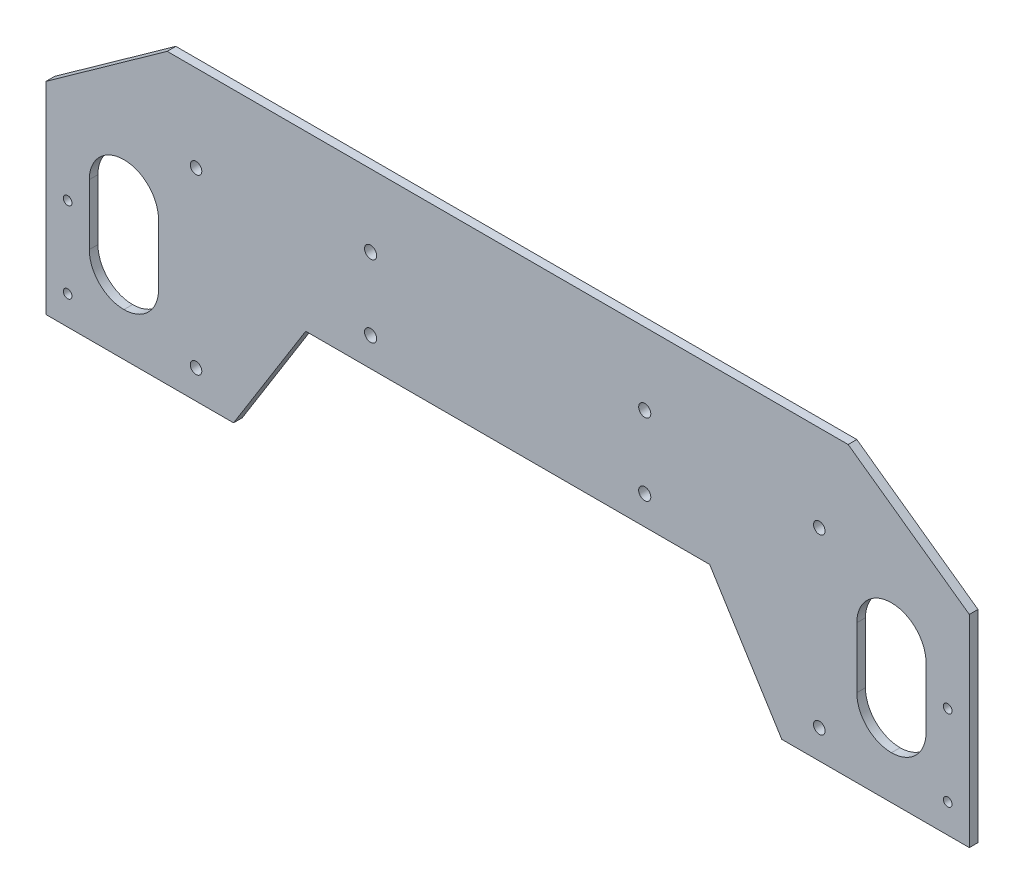
SolidWorks part; units mm, degrees
ref_plane "前视基准面" through (0, 0, 0) normal (0, 0, 1) x (1, 0, 0)
ref_plane "上视基准面" through (0, 0, 0) normal (0, 1, 0) x (1, 0, 0)
ref_plane "右视基准面" through (0, 0, 0) normal (1, 0, 0) x (0, 0, -1)
sketch "草图1" plane through (0, 0, 0) normal (0, 0, 1) x (1, 0, 0)
  line L1 (-160, 50) -> (160, 50)
  line L2 (-160, 50) -> (-160, -50)
  line L3 (-160, -50) -> (160, -50)
  line L4 (160, 50) -> (160, -50)
  line L5 (-160, 50) -> (160, -50) construction
  line L6 (-160, -50) -> (160, 50) construction
  point P0 (0, 0)
extrude "凸台-拉伸1" add sketch "草图1" along normal blind 3
ref_plane "基准面1" through (0, 0, 0) normal (1, 0, 0) x (0, 0, -1)
hole_wizard "Ø4.0 (4) 直径孔1" positions "草图3" profile "草图2" hole size "Ø4.0" standard "GB" end condition through all
sketch "草图3" plane through (0, 0, 0) normal (0, 0, -1) x (-1, 0, 0)
  line L0 (0, -50) -> (0, -40)
  line L1 (160, -50) -> (-160, -50) construction
  line L2 (0, -40) -> (108, -40)
  point P0 (108, -40)
sketch "草图2" plane through (-108, -40, 0) normal (1, 0, 0) x (0, 1, 0)
  line L0 (0, 0) -> (0, 3)
  line L1 (0, 3) -> (2, 3)
  line L2 (2, 3) -> (2, 0)
  line L5 (2, 0) -> (0, 0)
  line L11 (0, -6.35) -> (0, 107.95) construction
  dimension "通孔孔直径" = 4
  dimension "通孔孔深度" = 3
mirror "镜向1" about plane through (0, 0, 0) normal (1, 0, 0) of "Ø4.0 (4) 直径孔1"
hole_wizard "Ø4.2 (4.2) 直径孔1" positions "草图5" profile "草图4" hole size "Ø4.2" standard "GB" end condition through all
sketch "草图5" plane through (0, 0, 0) normal (0, 0, -1) x (-1, 0, 0)
  line L1 (0, -50) -> (47.5, -50)
  line L2 (160, -50) -> (-160, -50) construction
  line L3 (47.5, -50) -> (47.5, 0)
  point P7 (47.5, 0)
sketch "草图4" plane through (-47.5, 0, 0) normal (1, 0, 0) x (0, 1, 0)
  line L0 (0, 0) -> (0, 3)
  line L1 (0, 3) -> (2.1, 3)
  line L2 (2.1, 3) -> (2.1, 0)
  line L5 (2.1, 0) -> (0, 0)
  line L11 (0, -6.35) -> (0, 107.95) construction
  dimension "通孔孔直径" = 4.2
  dimension "通孔孔深度" = 3
pattern_linear "阵列(线性)1" count 2 spacing 95 along (1, 0, 0) count 2 spacing 25 along (0, 1, 0) of "Ø4.2 (4.2) 直径孔1"
sketch "草图6" plane through (0, 0, 0) normal (0, 0, -1) x (-1, 0, 0)
  line L0 (0, -50) -> (0, -10)
  line L1 (160, -50) -> (-160, -50) construction
  line L2 (0, -10) -> (70, -10)
  line L3 (70, -10) -> (95, -50)
  line L4 (95, -50) -> (0, -50)
extrude "切除-拉伸1" cut sketch "草图6" against normal blind 3
mirror "镜向2" about plane through (0, -50, 3) normal (1, 0, 0) of "切除-拉伸1"
sketch "草图8" plane through (0, 0, 0) normal (0, 0, -1) x (-1, 0, 0)
  line L0 (-160, -50) -> (-145, -50)
  line L1 (-95, -50) -> (-160, -50) construction
  line L2 (-145, -50) -> (-145, -35)
  line L3 (-145, -35) -> (-121, -35)
  line L4 (-121, -35) -> (-121, 10)
  line L5 (-121, 10) -> (-145, 10)
  line L6 (-145, 10) -> (-145, -35)
extrude "切除-拉伸6" cut sketch "草图8" against normal blind 3 contours L5 L6 L3 L4 region at (133, -12.5, 0)
mirror "镜向4" about plane through (0, 0, 0) normal (1, 0, 0) of "切除-拉伸6"
pattern_linear "阵列(线性)2" count 2 spacing 60 along (0, 1, 0) of "镜向1"
hole_wizard "Ø3.0 (3) 直径孔1" positions "草图10" profile "草图9" hole size "Ø3.0" standard "GB" end condition through all
sketch "草图10" plane through (0, 0, 3) normal (0, 0, 1) x (1, 0, 0)
  line L5 (-152.5, -40) -> (-152.5, -12)
  line L7 (-152.5, -50) -> (-152.5, -40)
  line L8 (-160, -50) -> (-95, -50) construction
  point P0 (-152.5, -40)
  point P2 (-152.5, -12)
sketch "草图9" plane through (-152.5, -40, 3) normal (1, 0, 0) x (0, -1, 0)
  line L0 (0, 0) -> (0, 3)
  line L1 (0, 3) -> (1.5, 3)
  line L2 (1.5, 3) -> (1.5, 0)
  line L5 (1.5, 0) -> (0, 0)
  line L11 (0, -6.35) -> (0, 107.95) construction
  dimension "通孔孔直径" = 3
  dimension "通孔孔深度" = 3
sketch "草图11" plane through (0, 0, 3) normal (0, 0, 1) x (1, 0, 0)
  line L0 (-160, 50) -> (-160, 20)
  line L1 (-160, 50) -> (-160, -50) construction
  line L2 (-160, 20) -> (-118, 50)
  line L3 (160, 50) -> (-160, 50) construction
  line L4 (-118, 50) -> (-160, 50)
  line L5 (-160, -50) -> (-160, 20)
  line M22 (160, 50) -> (-160, 50)
  line M23 (-160, 50) -> (-160, -50)
extrude "切除-拉伸8" cut sketch "草图11" against normal blind 3 contours L2 M23 M22 region at (-146, 40, 3)
mirror "镜向6" about plane through (0, 0, 0) normal (1, 0, 0) of "切除-拉伸8"
mirror "镜向7" about plane through (0, 0, 0) normal (1, 0, 0) of "Ø3.0 (3) 直径孔1"
fillet "圆角1" radius 12 8 edges at (145, -35, 1.5) (121, -35, 1.5) (145, 10, 1.5) (121, 10, 1.5) (-145, -35, 1.5) (-121, -35, 1.5) (-145, 10, 1.5) (-121, 10, 1.5)
